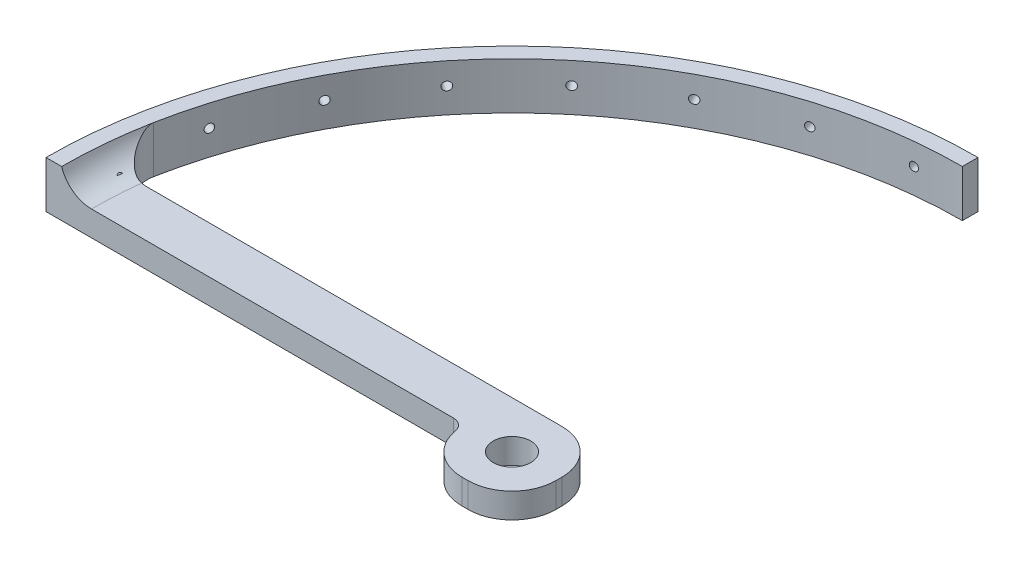
SolidWorks part; units mm, degrees
ref_plane "Front Plane" through (0, 0, 0) normal (0, 0, 1) x (1, 0, 0)
ref_plane "Top Plane" through (0, 0, 0) normal (0, 1, 0) x (1, 0, 0)
ref_plane "Right Plane" through (0, 0, 0) normal (1, 0, 0) x (0, 0, -1)
sketch "Sketch1" plane through (0, 0, 0) normal (0, 1, 0) x (1, 0, 0)
  line L0 (0, 0) -> (-149, 0) construction
  line L1 (0, 0) -> (0, 149) construction
  line L2 (0, 144) -> (0, 149)
  line L3 (-149, 0) -> (-144, 0)
  line L4 (-144, 0) -> (15, 0) construction
  line L5 (15, 0) -> (15, 1)
  line L6 (1, 15) -> (-131.6473, 15)
  line L7 (15, 0) -> (15, -1)
  line L8 (1, -15) -> (-1, -15)
  line L9 (-15, -1) -> (-15, 0)
  line L10 (-18.7482, 0) -> (-144, 0)
  arc A0 (0, 149) -> (-149, 0) centre (0, 0) ccw
  arc A1 (0, 144) -> (-141.4717, 26.8657) centre (0, 0) ccw
  circle A2 centre (0, 0) radius 144 construction
  circle A3 centre (0, 0) radius 149 construction
  arc A4 (1, 15) -> (15, 1) centre (1, 1) cw
  arc A5 (15, -1) -> (1, -15) centre (1, -1) cw
  arc A6 (-1, -15) -> (-14.8042, -3.3333) centre (-1, -1) cw
  arc A7 (-14.8042, -3.3333) -> (-18.7482, 0) centre (-18.7482, -4) ccw
  arc A8 (-141.4717, 26.8657) -> (-131.6473, 15) centre (-131.6473, 25) ccw
  circle A9 centre (0, 0) radius 6
  point P19 (15, -15)
  dimension "D1" = 298
  dimension "D3" = 149
  dimension "D8" = 14
  dimension "D9" = 4
  dimension "D10" = 10
  dimension "D11" = 12
  dimension "D4" = 159
  dimension "D5" = 15
  dimension "D6" = 30
  dimension "D7" = 15
  dimension "D2" = 5
extrude "Boss-Extrude1" add sketch "Sketch1" along normal blind 8 contours A8 A1 L2 A0 L3 L10 A7 A6 L8 A5 L7 L5 A4 L6 A9 region at (-93.3141, 0, -112.7023)
sketch "Sketch3" plane through (0, 0, 0) normal (0, -1, 0) x (1, 0, 0)
  line L0 (-149, 0) -> (-18.7482, 0) construction
  line L1 (-149, 0) -> (-144, 0)
  line L2 (0, -149) -> (0, -144)
  arc A1 (-149, 0) -> (0, -149) centre (0, 0) ccw
  arc A2 (-149, 0) -> (0, -149) centre (0, 0) ccw construction
  arc A3 (-144, 0) -> (0, -144) centre (0, 0) ccw
  dimension "D1" = 5
extrude "Boss-Extrude2" add sketch "Sketch3" along normal blind 7
fillet "Fillet1" radius 10 1 edges at (-143.3665, 0, -13.4922)
sketch "Sketch4" plane through (0, 0, 0) normal (0, -1, 0) x (-1, 0, 0)
  line L0 (0, 0) -> (143.3665, 13.4922) construction
  arc A0 (144, 0) -> (141.4717, 26.8657) centre (0, 0) ccw construction
ref_plane "Plane1" through (-148.3445, 0, -13.9607) normal (-0.9956, 0, -0.0937) x (-0.0937, 0, 0.9956)
sketch "Sketch5" plane through (-148.3445, 0, -13.9607) normal (-0.9956, 0, -0.0937) x (-0.0937, 0, 0.9956)
  circle A0 centre (0, 0) radius 1.35
  dimension "D1" = 2.7
extrude "Cut-Extrude1" cut sketch "Sketch5" against normal blind 10
sketch "Sketch6" plane through (0, 0, 0) normal (0, 0, 1) x (1, 0, 0)
  line L0 (0, 0) -> (0, -61.317) construction
pattern_circular "CirPattern2" count 32 over 360 about axis through (0, 0, 0) along (0, -1, 0) of "Cut-Extrude1" reverse direction yes
mirror "Mirror1" about plane through (0, 8, 0) normal (0, 1, 0) of bodies 105
sketch "Sketch7" plane through (0, -7, 0) normal (0, -1, 0) x (1, 0, 0)
  line L1 (168.5128, 172.3499) -> (-168.5128, 172.3499)
  line L2 (168.5128, 172.3499) -> (168.5128, -172.3499)
  line L3 (168.5128, -172.3499) -> (-168.5128, -172.3499)
  line L4 (-168.5128, 172.3499) -> (-168.5128, -172.3499)
  line L5 (168.5128, 172.3499) -> (-168.5128, -172.3499) construction
  line L6 (168.5128, -172.3499) -> (-168.5128, 172.3499) construction
  point P0 (0, 0)
extrude "Cut-Extrude2" cut sketch "Sketch7" against normal blind 15
